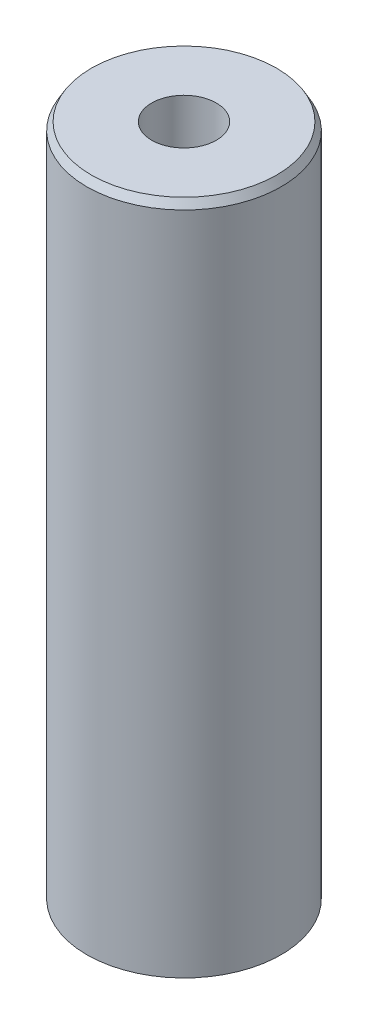
SolidWorks part; units mm, degrees
ref_plane "Front Plane" through (0, 0, 0) normal (0, 0, 1) x (1, 0, 0)
ref_plane "Top Plane" through (0, 0, 0) normal (0, 1, 0) x (1, 0, 0)
ref_plane "Right Plane" through (0, 0, 0) normal (1, 0, 0) x (0, 0, -1)
sketch "Sketch1" plane through (0, 0, 0) normal (0, 1, 0) x (1, 0, 0)
  circle A0 centre (0, 0) radius 45
  dimension "SHAFT_OD" = 90
extrude "Boss-Extrude1" add sketch "Sketch1" along normal blind 313.794
sketch "Sketch2" plane through (0, 0, 0) normal (0, 1, 0) x (1, 0, 0)
  circle A0 centre (0, 0) radius 14.9669
  dimension "BORE_D" = 29.9338
extrude "Cut-Extrude1" cut sketch "Sketch2" along normal through all
chamfer "Chamfer1" distance 3.6512 angle 30 2 edges at (0, 313.794, 45) (0, 0, 45) first distance on face at (0, 313.794, 45) first distance on face at (0, 0, 14.9669)
